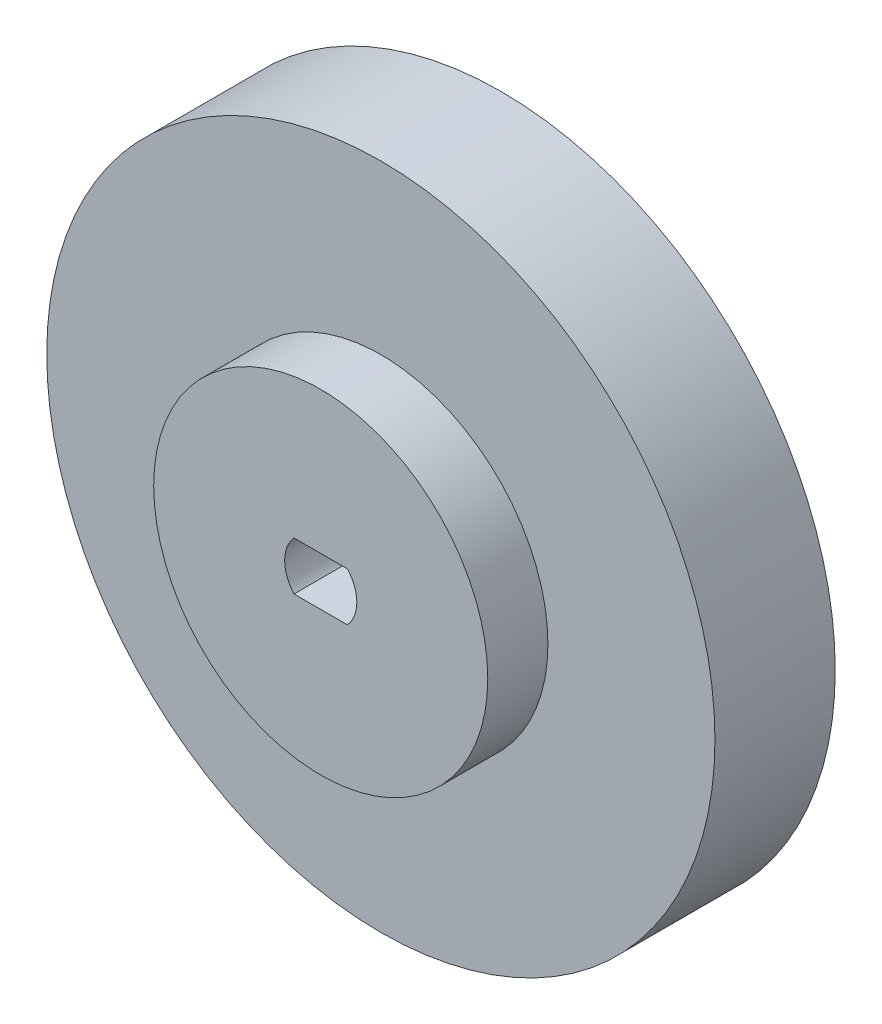
SolidWorks part; units mm, degrees
ref_plane "Front Plane" through (0, 0, 0) normal (0, 0, 1) x (1, 0, 0)
ref_plane "Top Plane" through (0, 0, 0) normal (0, 1, 0) x (1, 0, 0)
ref_plane "Right Plane" through (0, 0, 0) normal (1, 0, 0) x (0, 0, -1)
sketch "Sketch1" plane through (0, 0, 0) normal (0, 0, 1) x (1, 0, 0)
  line L0 (-34.1361, 0) -> (38.3541, 0) construction
  line L1 (0, 21.5067) -> (0, -21.6048) construction
  circle A0 centre (0, -0.049) radius 12.5
  dimension "D1" = 25
extrude "Boss-Extrude1" add sketch "Sketch1" along normal blind 18
sketch "Sketch2" plane through (0, 0, 18) normal (0, 0, 1) x (1, 0, 0)
  circle A0 centre (0, 0) radius 25
  dimension "D1" = 50
extrude "Boss-Extrude2" add sketch "Sketch2" against normal blind 9 from offset 4.5 offset against normal yes
sketch "Sketch3" plane through (0, 0, 18) normal (0, 0, 1) x (1, 0, 0)
  line L0 (-9.6925, 0) -> (15.432, 0) construction
  line L1 (-2, 1.8138) -> (2, 1.8138)
  line L2 (-2, -1.8138) -> (2, -1.8138)
  arc A0 (-2, 1.8138) -> (-2, -1.8138) centre (0, 0) ccw
  arc A1 (2, -1.8138) -> (2, 1.8138) centre (0, 0) ccw
  dimension "D1" = 5.4
  dimension "D2" = 4
extrude "Cut-Extrude1" cut sketch "Sketch3" against normal through all
